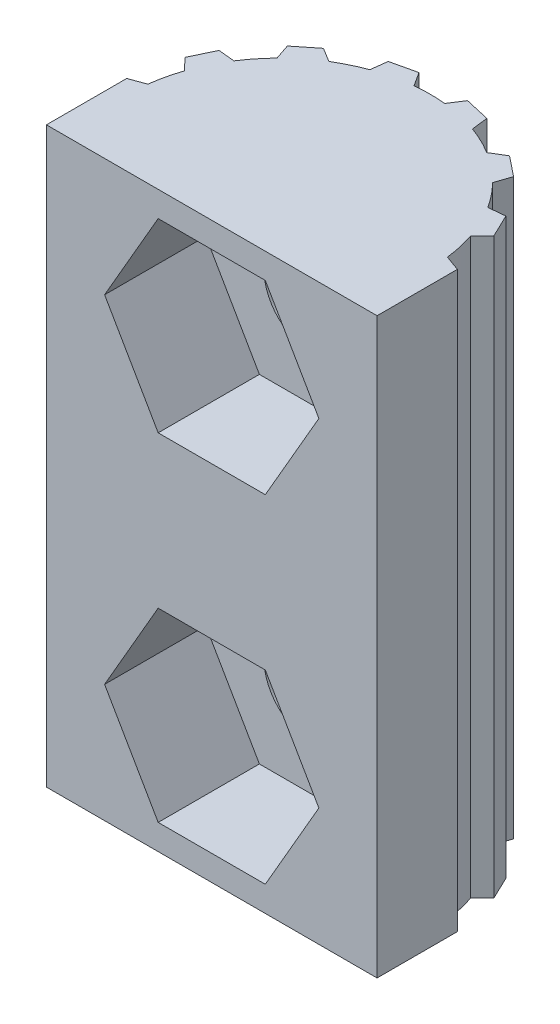
SolidWorks part; units mm, degrees
ref_plane "Front" through (0, 0, 0) normal (0, 0, 1) x (1, 0, 0)
ref_plane "Top" through (0, 0, 0) normal (0, 1, 0) x (1, 0, 0)
ref_plane "Right" through (0, 0, 0) normal (1, 0, 0) x (0, 0, -1)
sketch "Sketch1" plane through (0, 0, 0) normal (0, 1, 0) x (1, 0, 0)
  line L0 (-4.4736, 0) -> (4.4736, 0)
  arc A0 (4.4736, 0) -> (-4.4736, 0) centre (0, 0) ccw
  line B0 (-4.44, 0.5474) -> (-4.9, 0.38)
  line B1 (-4.9, 0.38) -> (-4.9, -0.38)
  line B2 (-4.9, -0.38) -> (-4.44, -0.5474)
  line B3 (-4.44, 0.5474) -> (-4.44, -0.5474)
  line B4 (-4.9, 0) -> (-4.44, 0) construction
  dimension "D1" = 4.9
  dimension "D2" = 4.4736
sketch_block_instance "MXL-Belt Tooth Profile-4"
sketch_block "MXL-Belt Tooth Profile" parameters "D1"=40, "D2"=0.46, "D3"=0.76
extrude "Boss-Extrude1" add sketch "Sketch1" along normal mid plane 17 contours A0 B3 L0 | B3 A0 L0 region at (-4.4535, 0, -0.2054) region at (0.0017, 0, -1.8993)
extrude "Boss-Extrude2" add sketch "Sketch1<3>" along normal up to surface and the other way up to surface contours B3 L0 A0 B0 B1 B2 region at (-4.6622, 0, 0.0061) up to face at (0, 8.5, -2.2368) other way up to face at (0, -8.5, -2.2368)
sketch "Sketch1<3>" plane through (0, 0, 0) normal (0, 1, 0) x (1, 0, 0) same geometry as "Sketch1"
pattern_circular "CirPattern1" count 8 over 180 about axis through (0, 8.5, 0) along (0, -1, 0) of "Boss-Extrude2"
sketch "Sketch4" plane through (0, 8.5, 0) normal (0, 1, 0) x (1, 0, 0)
  line L0 (-4.44, 0) -> (4.4736, 0) construction
  line L1 (-4.9, 0) -> (4.9, 0)
  line L4 (-4.9, 0.38) -> (-4.9, -0.38) construction
  line L5 (4.9, -0.38) -> (4.9, 0.38) construction
extrude "Cut-Extrude1" cut sketch "Sketch4" against normal through all and the other way through all flip side to cut
sketch "Sketch10" plane through (0, 0, 0) normal (0, 0, 1) x (1, 0, 0)
  line L4 (-4.9, -8.5) -> (4.9, -8.5)
  line L5 (4.9, -8.5) -> (4.9, 8.5)
  line L6 (4.9, 8.5) -> (-4.9, 8.5)
  line L7 (-4.9, 8.5) -> (-4.9, -8.5)
  line L8 (-4.9, -8.5) -> (4.9, -8.5)
  line L9 (4.9, -8.5) -> (4.9, 8.5)
  line L10 (4.9, 8.5) -> (-4.9, 8.5)
  line L11 (-4.9, 8.5) -> (-4.9, -8.5)
  dimension "D1" = 0
extrude "Boss-Extrude3" add sketch "Sketch10" along normal blind 2
sketch "Sketch5" plane through (0, 0, 2) normal (0, 0, 1) x (1, 0, 0)
  line L0 (0, -5) -> (0, 5) construction
  dimension "D1" = 10
hole_wizard "M2.5 Clearance Hole1" positions "Sketch7" profile "Sketch8" hole size "M2.5" standard "Ansi Metric" end condition through all
sketch "Sketch7" plane through (-2.1882, 1.7765, 2) normal (0, 0, 1) x (1, 0, 0)
  point P0 (2.1882, 3.2235)
  point P1 (2.1882, -6.7765)
sketch "Sketch8" plane through (0, 5, 2) normal (1, 0, 0) x (0, -1, 0)
  line L0 (0, 0) -> (0, 6.8617)
  line L1 (0, 6.8617) -> (1.45, 6.8617)
  line L2 (1.45, 6.8617) -> (1.45, 0)
  line L5 (1.45, 0) -> (0, 0)
  line L11 (0, -6.35) -> (0, 107.95) construction
  dimension "Thru Hole Dia." = 2.9
  dimension "Thru Hole Depth" = 6.8617
sketch "Sketch9" plane through (0, 0, 2) normal (0, 0, 1) x (1, 0, 0)
  line L1 (-3.1754, 5) -> (-1.5877, 2.25)
  line L2 (-1.5877, 2.25) -> (1.5877, 2.25)
  line L3 (1.5877, 2.25) -> (3.1754, 5)
  line L4 (3.1754, 5) -> (1.5877, 7.75)
  line L5 (1.5877, 7.75) -> (-1.5877, 7.75)
  line L6 (-1.5877, 7.75) -> (-3.1754, 5)
  line L7 (-3.1754, -5) -> (-1.5877, -7.75)
  line L8 (-1.5877, -7.75) -> (1.5877, -7.75)
  line L9 (1.5877, -7.75) -> (3.1754, -5)
  line L10 (3.1754, -5) -> (1.5877, -2.25)
  line L11 (1.5877, -2.25) -> (-1.5877, -2.25)
  line L12 (-1.5877, -2.25) -> (-3.1754, -5)
  circle A0 centre (0, 5) radius 2.75 construction
  circle A1 centre (0, -5) radius 2.75 construction
  dimension "D1" = 5.5
extrude "Cut-Extrude2" cut sketch "Sketch9" against normal blind 3
